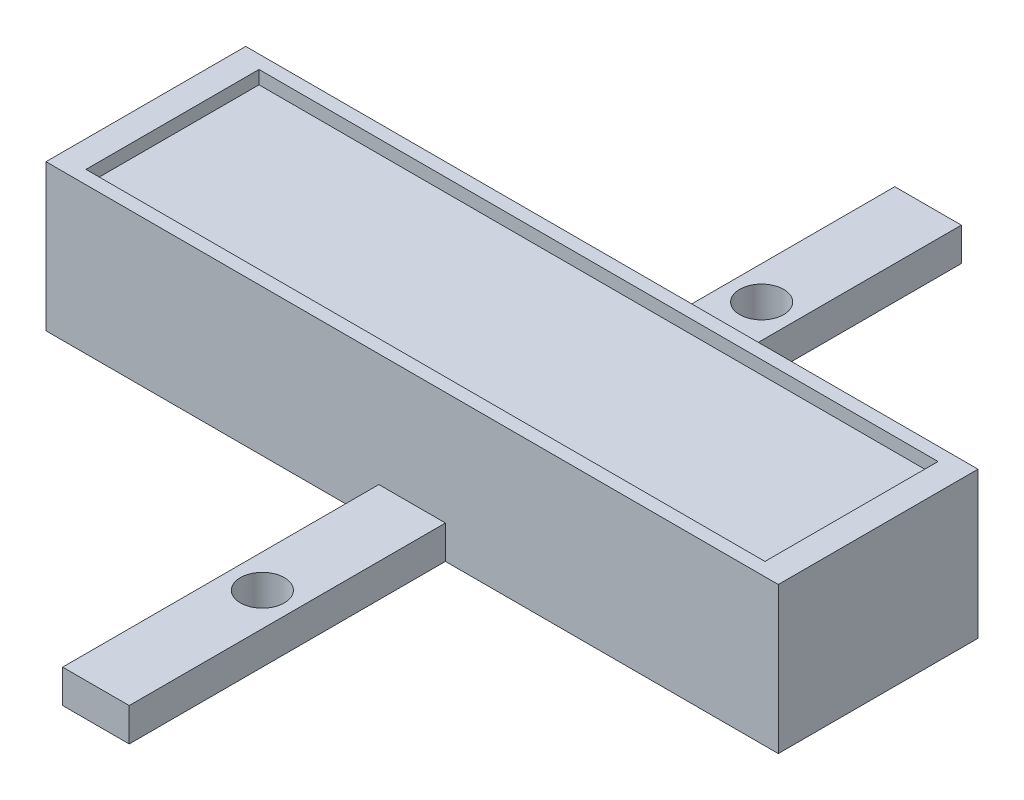
SolidWorks part; units mm, degrees
ref_plane "Front Plane" through (0, 0, 0) normal (0, 0, 1) x (1, 0, 0)
ref_plane "Top Plane" through (0, 0, 0) normal (0, 1, 0) x (1, 0, 0)
ref_plane "Right Plane" through (0, 0, 0) normal (1, 0, 0) x (0, 0, -1)
sketch "Sketch2" plane through (0, 0, 0) normal (0, 1, 0) x (1, 0, 0)
  line L1 (-55, -15) -> (55, -15)
  line L2 (-55, -15) -> (-55, 15)
  line L3 (-55, 15) -> (55, 15)
  line L4 (55, -15) -> (55, 15)
  line L5 (-55, -15) -> (55, 15) construction
  line L6 (-55, 15) -> (55, -15) construction
  point P0 (0, 0)
  point P6 (0, 0)
  point P7 (0, 0)
  point P8 (0, 0)
  point P9 (0, 0)
  point P10 (0, 0)
  point P11 (0, 0)
extrude "Boss-Extrude1" add sketch "Sketch2" along normal blind 22
sketch "Sketch3" plane through (0, 22, 0) normal (0, 1, 0) x (1, 0, 0)
  line L1 (-51, 13) -> (51, 13)
  line L2 (-51, 13) -> (-51, -13)
  line L3 (-51, -13) -> (51, -13)
  line L4 (51, 13) -> (51, -13)
  point P4 (0, 0)
  point P5 (0, 0)
  point P6 (0, 0)
  point P7 (0, 0)
  point P8 (0, 0)
  point P9 (0, 0)
  point P10 (0, 0)
  point P11 (0, 0)
  point P12 (0, 0)
  point P13 (0, 0)
  point P14 (0, 0)
  point P15 (0, 0)
  point P16 (0, 0)
  point P17 (0, 0)
  point P18 (0, 0)
extrude "Cut-Extrude1" cut sketch "Sketch3" against normal blind 2
sketch "Sketch4" plane through (0, 0, 0) normal (0, -1, 0) x (-1, 0, 0)
  line L0 (55, -15) -> (-55, -15) construction
  line L1 (5, -15) -> (-5, -15)
  line L2 (5, -15) -> (5, -62.5)
  line L3 (5, -62.5) -> (-5, -62.5)
  line L4 (-5, -15) -> (-5, -62.5)
extrude "Boss-Extrude3" add sketch "Sketch4" against normal blind 5 separate body
hole_wizard "M6 Clearance Hole1" positions "3DSketch3" profile "Sketch7" hole size "M6" standard "ANSI Metric" end condition through all
sketch3d "3DSketch3"
  point P0 (0, 5, 37.5)
sketch "Sketch7" plane through (0, 5, 37.5) normal (1, 0, 0) x (0, 0, 1)
  line L0 (0, 0) -> (0, 5)
  line L1 (0, 5) -> (3.3, 5)
  line L2 (3.3, 5) -> (3.3, 0)
  line L5 (3.3, 0) -> (0, 0)
  line L11 (0, -6.35) -> (0, 107.95) construction
  dimension "Thru Hole Dia." = 6.6
  dimension "Thru Hole Depth" = 5
sketch "Sketch13" plane through (0, 0, 0) normal (0, -1, 0) x (-1, 0, 0)
  line L0 (-55, 15) -> (55, 15) construction
  line L1 (5, 15) -> (-5, 15)
  line L2 (5, 15) -> (5, 62.5)
  line L3 (5, 62.5) -> (-5, 62.5)
  line L4 (-5, 15) -> (-5, 62.5)
extrude "Boss-Extrude4" add sketch "Sketch13" against normal blind 5 separate body
hole_wizard "M6 Clearance Hole2" positions "3DSketch4" profile "Sketch14" hole size "M6" standard "ANSI Metric" end condition through all
sketch3d "3DSketch4"
  point P0 (0, 5, -37.5)
sketch "Sketch14" plane through (0, 5, -37.5) normal (1, 0, 0) x (0, 0, 1)
  line L0 (0, 0) -> (0, 5)
  line L1 (0, 5) -> (3.3, 5)
  line L2 (3.3, 5) -> (3.3, 0)
  line L5 (3.3, 0) -> (0, 0)
  line L11 (0, -6.35) -> (0, 107.95) construction
  dimension "Thru Hole Dia." = 6.6
  dimension "Thru Hole Depth" = 5
